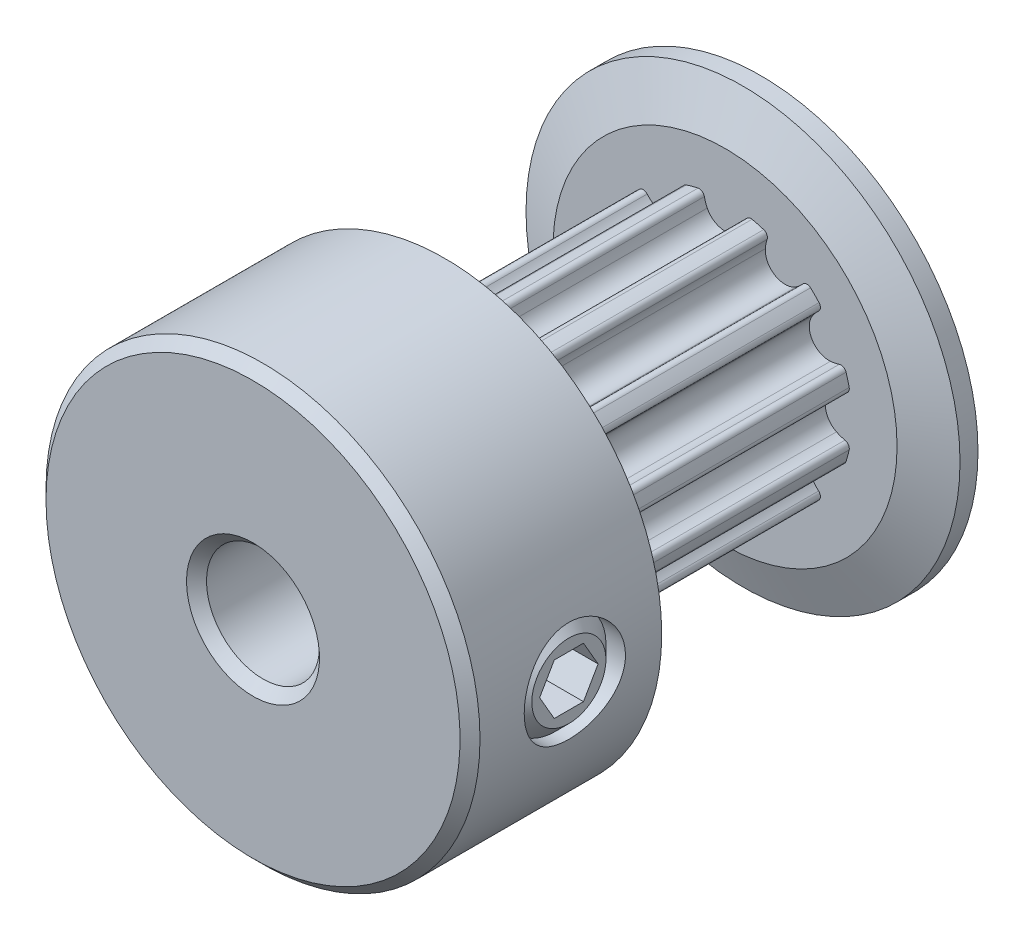
SolidWorks part; units mm, degrees
ref_plane "Front Plane" through (0, 0, 0) normal (0, 0, 1) x (1, 0, 0)
ref_plane "Top Plane" through (0, 0, 0) normal (0, 1, 0) x (1, 0, 0)
ref_plane "Right Plane" through (0, 0, 0) normal (1, 0, 0) x (0, 0, -1)
sketch "Sketch1" plane through (0, 0, 0) normal (0, 0, 1) x (1, 0, 0)
  line L1 (-1.6491, 2.8185) -> (1.6491, 2.8185) construction
  line L4 (0, 0) -> (0, 2.8185) construction
  line L5 (0, 2.8185) -> (0, 9.5178) construction
  line L6 (0, 3.8225) -> (1.9303, 3.2993) construction
  line L7 (1.9303, 3.2993) -> (2.4111, 3.018) construction
  line L8 (1.9303, 3.2993) -> (1.6491, 2.8185) construction
  line L9 (-1.9303, 3.2993) -> (-1.6491, 2.8185) construction
  line L10 (-1.8021, 3.08) -> (-3.5667, 6.096)
  line L11 (-3.5667, 6.096) -> (3.5667, 6.096)
  line L12 (3.5667, 6.096) -> (1.8021, 3.08)
  circle A0 centre (0, 0) radius 3.8225 construction
  circle A1 centre (0, 0) radius 6.096 construction
  circle A2 centre (0, 0) radius 3.5685 construction
  arc A3 (-0.4989, 3.1303) -> (0.4989, 3.1303) centre (0, 3.3735) ccw
  arc A4 (-0.4989, 3.1303) -> (-0.5801, 3.37) centre (0.4, 3.5685) cw
  arc A5 (-1.8021, 3.08) -> (-0.759, 3.4868) centre (0, 0) cw
  arc A6 (-0.5801, 3.37) -> (-0.759, 3.4868) centre (-0.7271, 3.3403) ccw
  arc A7 (1.8021, 3.08) -> (0.759, 3.4868) centre (0, 0) ccw
  arc A8 (0.5801, 3.37) -> (0.759, 3.4868) centre (0.7271, 3.3403) cw
  arc A9 (0.4989, 3.1303) -> (0.5801, 3.37) centre (-0.4, 3.5685) ccw
  point P6 (0, 20.9083)
  point P11 (0, 3.8225)
  point P13 (0, 6.096)
  point P14 (0, 3.5685)
  dimension "D1" = 11.3905
  dimension "D2" = 5.6953
sketch "Sketch2" plane through (0, 0, 0) normal (1, 0, 0) x (0, 0, -1)
  line L0 (-7.135, 1.5875) -> (7.135, 1.5875)
  line L1 (-7.135, 1.5875) -> (-7.135, 6.096)
  line L2 (-1.75, 6.096) -> (-7.135, 6.096)
  line L3 (-2.255, 1.5875) -> (-2.255, 6.096) construction
  line L4 (-2.255, 6.096) -> (-1.245, 6.096) construction
  line L5 (-1.245, 6.096) -> (-1.245, 3.5685) construction
  line L6 (-1.245, 3.5685) -> (6.125, 3.5685)
  line L7 (6.125, 3.5685) -> (6.125, 6.096) construction
  line L8 (6.125, 6.096) -> (7.135, 6.096) construction
  line L9 (7.135, 6.096) -> (7.135, 1.5875)
  line L10 (-7.135, 0) -> (7.135, 0) construction
  line L11 (6.63, 6.096) -> (6.125, 4.8323)
  line L12 (-1.245, 4.8323) -> (-1.75, 6.096)
  line L14 (-1.245, 4.8323) -> (-1.245, 3.5685)
  line L15 (6.125, 3.5685) -> (6.125, 4.8323)
  line L16 (6.63, 6.096) -> (7.135, 6.096)
  arc A0 (-1.245, 4.8323) -> (-1.75, 6.096) centre (-3.0788, 4.8323) ccw construction
  arc A1 (6.125, 4.8323) -> (6.63, 6.096) centre (7.9588, 4.8323) cw construction
  point P12 (-1.245, 4.8323)
  point P14 (-1.75, 6.096)
  point P20 (6.125, 4.8323)
  point P21 (6.63, 6.096)
  point P25 (6.125, 0)
  point P26 (-1.245, 0)
  dimension "OA" = 14.27
  dimension "Bore" = 3.175
  dimension "Outside Width" = 8.38
  dimension "Inside Width" = 7.37
revolve "Revolve1" add sketch "Sketch2" angle 360 mid plane about L10
sketch "Sketch3" plane through (0, 0, 0) normal (0, 0, 1) x (1, 0, 0)
  line L6 (3.5667, 6.096) -> (-3.5667, 6.096)
  line L7 (1.8021, 3.08) -> (3.5667, 6.096)
  line L8 (-3.5667, 6.096) -> (-1.8021, 3.08)
  line L9 (3.5667, 6.096) -> (-3.5667, 6.096)
  line L10 (1.8021, 3.08) -> (3.5667, 6.096)
  line L11 (-3.5667, 6.096) -> (-1.8021, 3.08)
  arc A8 (1.8021, 3.08) -> (0.759, 3.4868) centre (0, 0) ccw
  arc A9 (0.759, 3.4868) -> (0.5801, 3.37) centre (0.7271, 3.3403) ccw
  arc A10 (0.4989, 3.1303) -> (0.5801, 3.37) centre (-0.4, 3.5685) ccw
  arc A11 (-0.4989, 3.1303) -> (0.4989, 3.1303) centre (0, 3.3735) ccw
  arc A12 (-0.5801, 3.37) -> (-0.4989, 3.1303) centre (0.4, 3.5685) ccw
  arc A13 (-0.5801, 3.37) -> (-0.759, 3.4868) centre (-0.7271, 3.3403) ccw
  arc A14 (-0.759, 3.4868) -> (-1.8021, 3.08) centre (0, 0) ccw
  arc A15 (1.8021, 3.08) -> (0.759, 3.4868) centre (0, 0) ccw
  arc A16 (0.759, 3.4868) -> (0.5801, 3.37) centre (0.7271, 3.3403) ccw
  arc A17 (0.4989, 3.1303) -> (0.5801, 3.37) centre (-0.4, 3.5685) ccw
  arc A18 (-0.4989, 3.1303) -> (0.4989, 3.1303) centre (0, 3.3735) ccw
  arc A19 (-0.5801, 3.37) -> (-0.4989, 3.1303) centre (0.4, 3.5685) ccw
  arc A20 (-0.5801, 3.37) -> (-0.759, 3.4868) centre (-0.7271, 3.3403) ccw
  arc A21 (-0.759, 3.4868) -> (-1.8021, 3.08) centre (0, 0) ccw
  dimension "D1" = 0
extrude "Cut-Extrude1" cut sketch "Sketch3" against normal up to vertex (6.125 mm away) from vertex up to point (0, 3.5685, -6.125) starting at point (0, 3.5685, 1.245)
pattern_circular "CirPattern1" count 12 over 360 about axis through (0, 0, 7.135) along (0, 0, 1) of "Cut-Extrude1"
sketch "Sketch4" plane through (0, 0, 0) normal (1, 0, 0) x (0, -1, 0)
  line L0 (0, -1.245) -> (0, -7.135) construction
  line L1 (-1.5875, -7.135) -> (1.5875, -7.135) construction
  line L2 (4.8323, -1.245) -> (-4.8323, -1.245) construction
  circle A0 centre (0, -4.19) radius 1.4224
extrude "Cut-Extrude2" cut sketch "Sketch4" along normal through all
ref_plane "Plane1" through (0, 0, 4.19) normal (0, 0, 1) x (1, 0, 0)
sketch "Sketch5" plane through (0, 0, 4.19) normal (0, 0, 1) x (1, 0, 0)
  line L0 (0, 0) -> (0, 6.096) construction
  line L1 (1.5875, -1.0414) -> (1.5875, 0)
  line L2 (1.9685, -1.4224) -> (5.5467, -1.4224)
  line L3 (1.5875, 0) -> (6.096, 0) construction
  line L4 (1.5875, 0) -> (5.9277, 0)
  line L5 (5.9277, 0) -> (5.9277, -1.0414)
  line L6 (1.9685, -1.4224) -> (1.5875, -1.0414)
  line L7 (5.9277, -1.0414) -> (5.5467, -1.4224)
  circle A0 centre (0, 0) radius 6.096 construction
  circle A1 centre (0, 0) radius 1.5875 construction
  point P2 (1.5875, -1.4224)
  point P11 (5.9277, -1.4224)
revolve "Revolve2" add sketch "Sketch5" angle 360 mid plane about L4
sketch "Sketch6" plane through (5.9277, 5.3841, 0) normal (-1, 0, 0) x (0, -1, 0)
  line L1 (5.3841, 5.0112) -> (4.6729, 4.6006)
  line L2 (4.6729, 4.6006) -> (4.6729, 3.7794)
  line L3 (4.6729, 3.7794) -> (5.3841, 3.3688)
  line L4 (5.3841, 3.3688) -> (6.0953, 3.7794)
  line L5 (6.0953, 3.7794) -> (6.0953, 4.6006)
  line L6 (6.0953, 4.6006) -> (5.3841, 5.0112)
  circle A0 centre (5.3841, 4.19) radius 0.7112 construction
  dimension "D1" = 1.4224
extrude "Cut-Extrude3" cut sketch "Sketch6" along normal blind 1.0668
chamfer "Chamfer1" distance 0.2807 angle 45 2 edges at (1.5875, 0, 7.135) (6.096, 0, 7.135)
ref_axis "Center Axis 1" through (0, 0, -7.135) along (0, 0, 1)
ref_plane "Contact Plane 1" through (0, 0, 7.135) normal (0, 0, 1) x (1, 0, 0)
ref_plane "Contact Plane 2" through (0, 0, -7.135) normal (0, 0, -1) x (-1, 0, 0)
equation "\"D2@Sketch1\"= \"D1@Sketch1\" / 2"
equation "\"D1@Sketch6\" = \"Set Screw@Sketch4\" / 2"
equation "\"D1@Cut-Extrude3\" = \"D1@Sketch6\"*.75"
